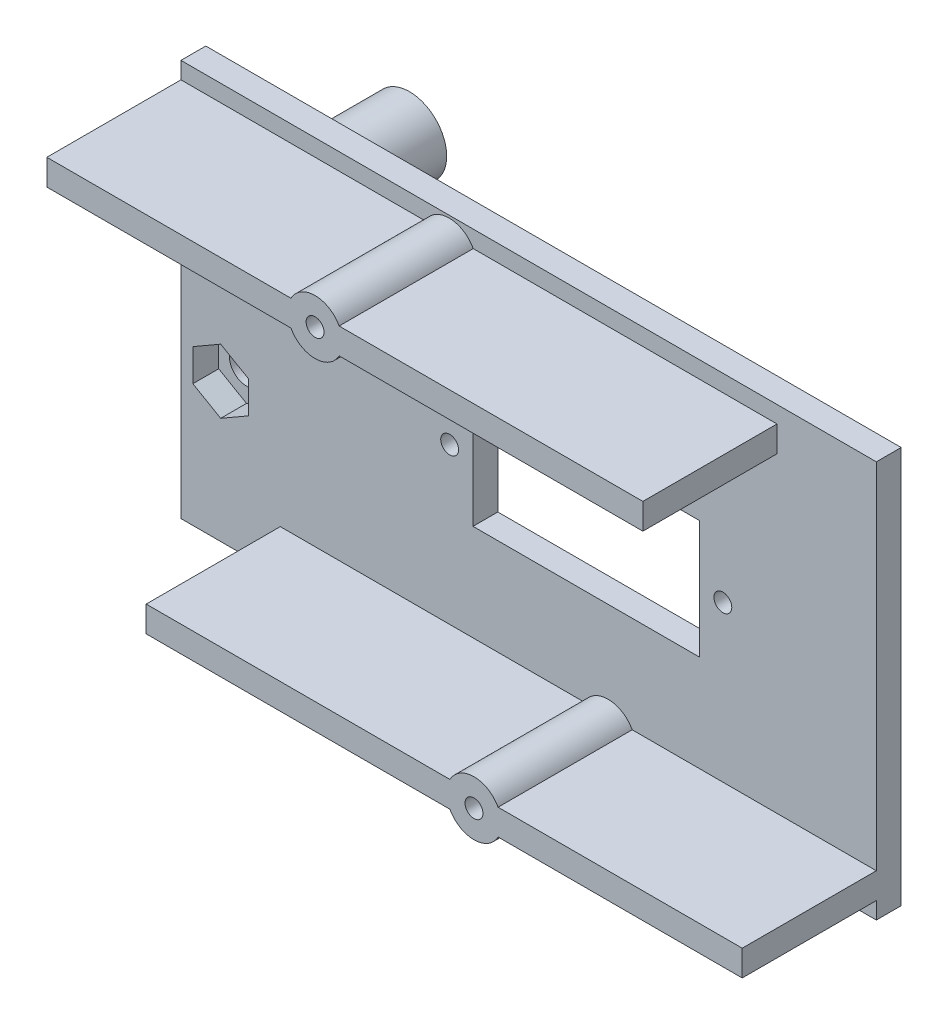
SolidWorks part; units mm, degrees
ref_plane "Front Plane" through (0, 0, 0) normal (0, 0, 1) x (1, 0, 0)
ref_plane "Top Plane" through (0, 0, 0) normal (0, 1, 0) x (1, 0, 0)
ref_plane "Right Plane" through (0, 0, 0) normal (1, 0, 0) x (0, 0, -1)
sketch "Sketch1" plane through (0, 0, 0) normal (0, 0, 1) x (1, 0, 0)
  line L0 (-35, -19.975) -> (35, -19.975)
  line L1 (35, -19.975) -> (35, 19.975)
  line L2 (35, 19.975) -> (-35, 19.975)
  line L3 (-35, 19.975) -> (-35, -19.975)
extrude "Boss-Extrude1" add sketch "Sketch1" along normal blind 2.5 from offset 2.5 offset against normal yes
sketch "Sketch2" plane through (0, 0, 0) normal (0, 0, 1) x (1, 0, 0)
  line L0 (-35, 15.675) -> (25, 15.675)
  line L1 (25, 15.675) -> (25, 18.275)
  line L2 (25, 18.275) -> (-35, 18.275)
  line L3 (-35, 18.275) -> (-35, 15.675)
extrude "Boss-Extrude2" add sketch "Sketch2" along normal blind 13.5
sketch "Sketch3" plane through (0, 0, 0) normal (0, 0, 1) x (1, 0, 0)
  line L0 (-25, -18.275) -> (35, -18.275)
  line L1 (35, -18.275) -> (35, -15.675)
  line L2 (35, -15.675) -> (-25, -15.675)
  line L3 (-25, -15.675) -> (-25, -18.275)
extrude "Boss-Extrude3" add sketch "Sketch3" along normal blind 13.5
sketch "Sketch4" plane through (0, 0, 0) normal (0, 0, 1) x (1, 0, 0)
  circle A0 centre (-8, 16.975) radius 2.75
  circle A1 centre (8, -16.975) radius 2.75
extrude "Boss-Extrude4" add sketch "Sketch4" along normal blind 13.5
sketch "Sketch5" plane through (0, 0, 0) normal (0, 0, 1) x (1, 0, 0)
  circle A0 centre (-31, 6) radius 3.75
  circle A1 centre (-31, -6) radius 3.75
extrude "Boss-Extrude5" add sketch "Sketch5" along normal blind 16.5 from offset 19 offset against normal yes
sketch "Sketch6" plane through (0, 0, 0) normal (0, 0, 1) x (1, 0, 0)
  line L0 (-5.6, -5.95) -> (17.2, -5.95)
  line L1 (17.2, -5.95) -> (17.2, 5.95)
  line L2 (17.2, 5.95) -> (-5.6, 5.95)
  line L3 (-5.6, 5.95) -> (-5.6, -5.95)
extrude "Cut-Extrude1" cut sketch "Sketch6" against normal through all and the other way through all
sketch "Sketch7" plane through (0, 0, 0) normal (0, 0, 1) x (1, 0, 0)
  circle A0 centre (-7.95, 0) radius 0.9
  circle A1 centre (19.55, 0) radius 0.9
extrude "Cut-Extrude2" cut sketch "Sketch7" against normal through all and the other way through all
sketch "Sketch8" plane through (0, 0, 0) normal (0, 0, 1) x (1, 0, 0)
  circle A0 centre (-8, 16.975) radius 0.9
  circle A1 centre (8, -16.975) radius 0.9
extrude "Cut-Extrude3" cut sketch "Sketch8" against normal through all and the other way through all
sketch "Sketch9" plane through (0, 0, 0) normal (0, 0, 1) x (1, 0, 0)
  circle A0 centre (-31, 6) radius 1.725
  circle A1 centre (-31, -6) radius 1.725
extrude "Cut-Extrude4" cut sketch "Sketch9" against normal through all and the other way through all
sketch "Sketch10" plane through (0, 0, 0) normal (0, 0, 1) x (1, 0, 0)
  line L0 (-28.2, 7.6166) -> (-31, 9.2332)
  line L1 (-31, 9.2332) -> (-33.8, 7.6166)
  line L2 (-33.8, 7.6166) -> (-33.8, 4.3834)
  line L3 (-33.8, 4.3834) -> (-31, 2.7668)
  line L4 (-31, 2.7668) -> (-28.2, 4.3834)
  line L5 (-28.2, 4.3834) -> (-28.2, 7.6166)
  line L6 (-28.2, -4.3834) -> (-31, -2.7668)
  line L7 (-31, -2.7668) -> (-33.8, -4.3834)
  line L8 (-33.8, -4.3834) -> (-33.8, -7.6166)
  line L9 (-33.8, -7.6166) -> (-31, -9.2332)
  line L10 (-31, -9.2332) -> (-28.2, -7.6166)
  line L11 (-28.2, -7.6166) -> (-28.2, -4.3834)
extrude "Cut-Extrude5" cut sketch "Sketch10" along normal blind 2.6 from offset 2.6 offset against normal yes
